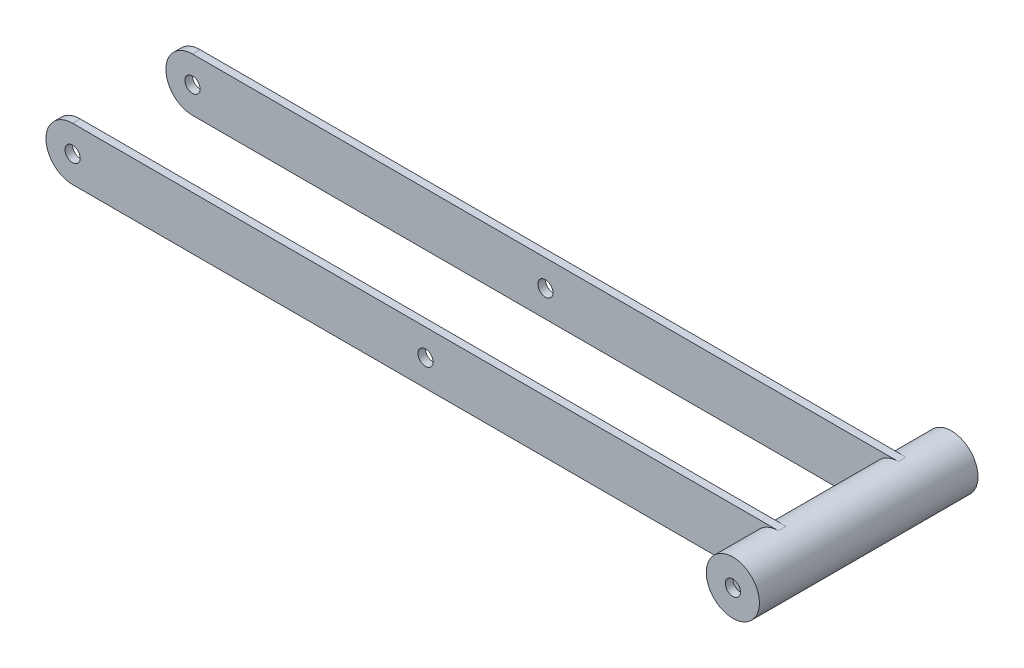
SolidWorks part; units mm, degrees
ref_plane "Front Plane" through (0, 0, 0) normal (0, 0, 1) x (1, 0, 0)
ref_plane "Top Plane" through (0, 0, 0) normal (0, 1, 0) x (1, 0, 0)
ref_plane "Right Plane" through (0, 0, 0) normal (1, 0, 0) x (0, 0, -1)
sketch "Sketch3" plane through (0, 0, 0) normal (0, 1, 0) x (1, 0, 0)
  line L1 (-250, 42) -> (250, 42)
  line L2 (-250, 42) -> (-250, -42)
  line L3 (-250, -42) -> (250, -42)
  line L4 (250, 42) -> (250, -42)
  line L5 (-250, 42) -> (250, -42) construction
  line L6 (-250, -42) -> (250, 42) construction
  point P0 (0, 0)
  dimension "D1" = 84
  dimension "D2" = 500
extrude "Boss-Extrude3" add sketch "Sketch3" along normal mid plane 35 contours L1 L4 L3 L2
sketch "Sketch4" plane through (0, 17.5, 0) normal (0, 1, 0) x (1, 0, 0)
  line L0 (-250, 42) -> (250, 42) construction
  line L1 (-250, 37) -> (250, 37)
  line L2 (-250, 37) -> (-250, -37)
  line L3 (-250, -37) -> (250, -37)
  line L4 (250, 37) -> (250, -37)
  line L5 (-250, 37) -> (250, -37) construction
  line L6 (-250, -37) -> (250, 37) construction
  point P0 (0, 0)
  dimension "D1" = 5
  dimension "D2" = 500
fillet "Fillet2" radius 17.5 4 edges at (250, -17.5, 0) (250, 17.5, 0) (-250, -17.5, 0) (-250, 17.5, 0)
extrude "Cut-Extrude2" cut sketch "Sketch4" against normal blind 35
sketch "Sketch10" plane through (0, 0, -42) normal (0, 0, -1) x (-1, 0, 0)
  line L0 (232.5, 17.5) -> (232.5, -17.5) construction
  arc A0 (232.5, -17.5) -> (250, 0) centre (232.5, 0) ccw construction
  circle A1 centre (232.5, 0) radius 5
  dimension "D1" = 10
extrude "Cut-Extrude5" cut sketch "Sketch10" against normal through all contours A1
sketch "Sketch9" plane through (0, 0, -42) normal (0, 0, -1) x (-1, 0, 0)
  circle A0 centre (0, 0) radius 5
  dimension "D1" = 10
extrude "Cut-Extrude4" cut sketch "Sketch9" against normal through all
sketch "Sketch5" plane through (0, 0, 0) normal (0, 0, 1) x (1, 0, 0)
  line L0 (232.5, 17.5) -> (232.5, -17.5) construction
  circle A0 centre (232.5, 0) radius 17.5
extrude "Boss-Extrude4" add sketch "Sketch5" along normal mid plane 144
sketch "Sketch8" plane through (0, 0, -72) normal (0, 0, -1) x (-1, 0, 0)
  line L0 (-250, 0) -> (-215, 0) construction
  circle A0 centre (-232.5, 0) radius 17.5 construction
  circle A1 centre (-232.5, 0) radius 5
  dimension "D1" = 10
extrude "Cut-Extrude3" cut sketch "Sketch8" against normal blind 5
mirror "Mirror1" about plane through (0, 0, 0) normal (0, 0, 1) of "Cut-Extrude3"
